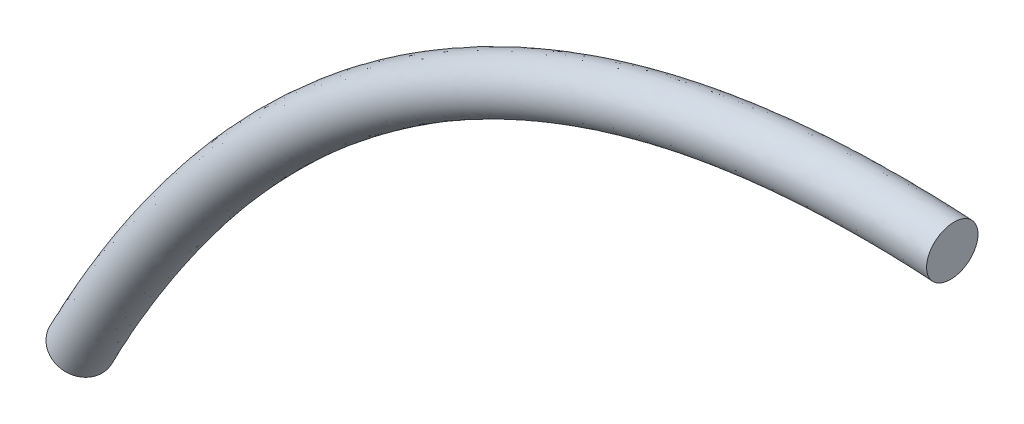
SolidWorks part; units mm, degrees
material "Custom Plastic"
ref_plane "X-Y Datum" through (0, 0, 0) normal (0, 0, 1) x (1, 0, 0)
ref_plane "X-Z Datum" through (0, 0, 0) normal (0, 1, 0) x (1, 0, 0)
ref_plane "Y-Z Datum" through (0, 0, 0) normal (1, 0, 0) x (0, 0, -1)
sketch3d "3DSketch1"
  circle A0 centre (-244.2256, -166.5107, 163.3218) radius 2.9 construction
  circle A1 centre (-70.1324, -53.4906, 181.6608) radius 2.5781 construction
  circle A3 centre (-244.2256, -166.5107, 163.3218) radius 3.475 construction
  spline S0 degree 2 poles (-244.2256, -166.5107, 163.3218) (-172.691, -46.8631, 181.8159) (-66.6135, -53.6824, 181.6608) knots 0 0 0 1 1 1
  point P0 (-244.2256, -166.5107, 163.3218)
  point P1 (-70.1324, -53.4906, 181.6608)
  point P4 (-246.0339, -168.7779, 163.3218)
  point P8 (-72.6964, -53.7601, 181.6608)
  point P16 (-246.3925, -169.2274, 163.3218)
sweep "Sweep1" add path "3DSketch1" circular profile diameter 9.398 parameters "D3"=9.398
